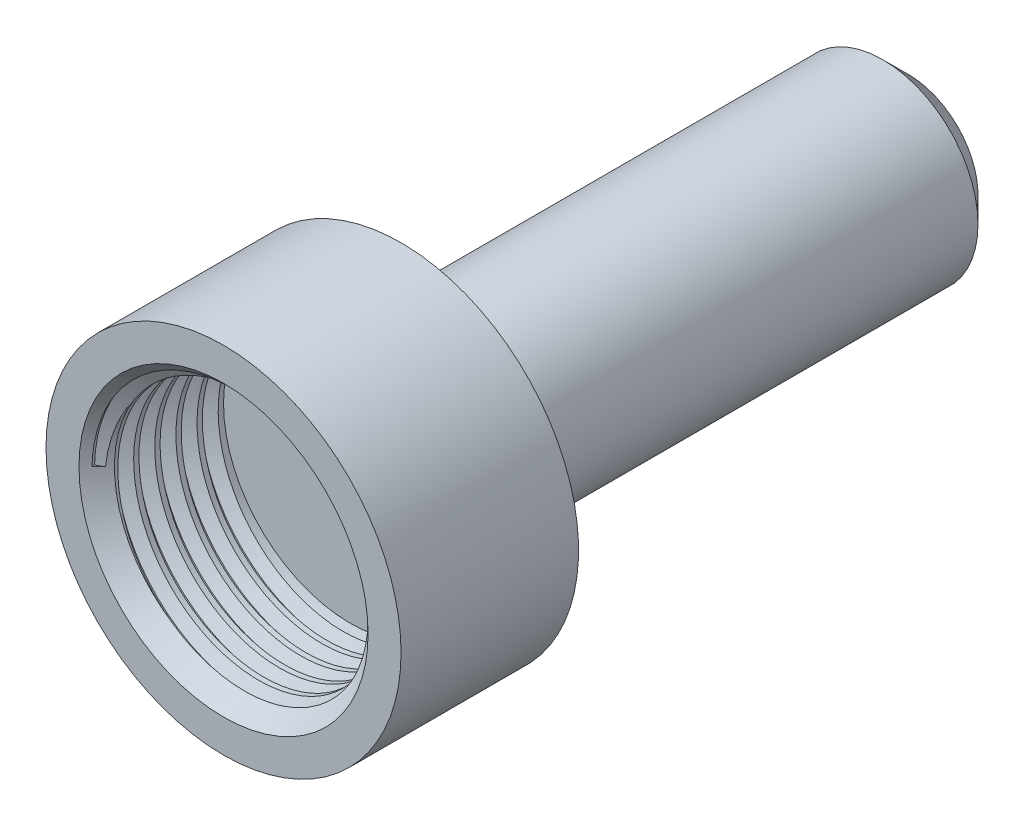
SolidWorks part; units mm, degrees
material "Plain Carbon Steel"
ref_plane "Front Plane" through (0, 0, 0) normal (0, 0, 1) x (1, 0, 0)
ref_plane "Top Plane" through (0, 0, 0) normal (0, 1, 0) x (1, 0, 0)
ref_plane "Right Plane" through (0, 0, 0) normal (1, 0, 0) x (0, 0, -1)
sketch "Sketch1" plane through (0, 0, 0) normal (0, 0, 1) x (1, 0, 0)
  circle A0 centre (0, 0) radius 6.35
  circle A1 centre (0, 0) radius 8.89
  dimension "D1" = 12.7
  dimension "D2" = 2.54
extrude "Boss-Extrude1" add sketch "Sketch1" along normal blind 6.35
sketch "Sketch2" plane through (0, 0, 0) normal (0, 0, -1) x (-1, 0, 0)
  circle A0 centre (0, 0) radius 8.89
  circle A1 centre (0, 0) radius 8.89 construction
extrude "Boss-Extrude2" add sketch "Sketch2" along normal blind 2.54
sketch "Sketch3" plane through (0, 0, -2.54) normal (0, 0, -1) x (-1, 0, 0)
  circle A0 centre (0, 0) radius 4.7625
  dimension "D1" = 9.525
extrude "Boss-Extrude3" add sketch "Sketch3" along normal blind 25.4
fillet "Fillet1" radius 2.54 1 edges at (-4.7625, 0, -2.54)
chamfer "Chamfer1" distance 1.27 angle 45 1 edges at (-4.7625, 0, -27.94)
thread "Thread1" pitch 1.0583 method cut profile "Thread Profile1" start angle 0, offset 0, length 5.842, pitch 1.0583, diameter 12.7
ref_plane "Plane1" through (-6.35, 0, 6.35) normal (0, -1, 0) x (-1, 0, 0)
sketch "Thread Profile1" plane through (-6.35, 0, 6.35) normal (0, -1, 0) x (-1, 0, 0)
  line L0 (0, 0) -> (0, 1.0583) construction
  line L1 (0, 0) -> (0.5728, 0.3307)
  line L2 (0.5728, 0.3307) -> (0.5728, 0.463)
  line L3 (0.5728, 0.463) -> (0, 0.7937)
  line L4 (0.5728, 0.3969) -> (0, 0.3969) construction
  line L11 (0, 0) -> (0, 0.7937)
  point P2 (0, 0)
  dimension "Pitch" = 1.0583
  dimension "Profile_Angle" = 60
  dimension "Profile_Land" = 0.1323
  dimension "Profile_Height" = 0.5728
sketch "Sketch7" plane through (0, 0, 0) normal (1, 0, 0) x (0, 0, -1)
  line L0 (0, 0) -> (-7.9394, 0) construction
  line L1 (-4.953, -5.842) -> (-6.477, -7.366)
  line L2 (-6.477, -7.366) -> (-6.477, -5.842)
  line L3 (-6.477, -5.842) -> (-4.953, -5.842)
  line L4 (-6.35, 8.89) -> (-6.35, -8.89) construction
  dimension "D1" = 5.842
  dimension "D2" = 1.524
  dimension "D3" = 0.127
revolve "Cut-Revolve1" cut sketch "Sketch7" angle 360 about L0
